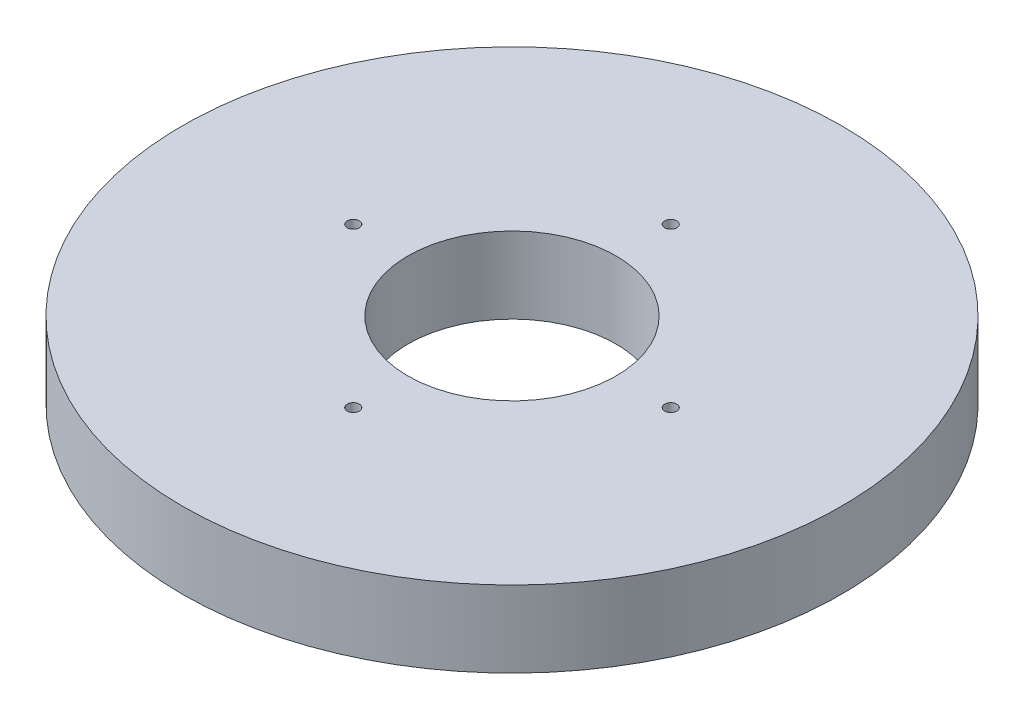
SolidWorks part; units mm, degrees
ref_plane "Front Plane" through (0, 0, 0) normal (0, 0, 1) x (1, 0, 0)
ref_plane "Top Plane" through (0, 0, 0) normal (0, 1, 0) x (1, 0, 0)
ref_plane "Right Plane" through (0, 0, 0) normal (1, 0, 0) x (0, 0, -1)
sketch "Sketch1" plane through (0, 0, 0) normal (0, 1, 0) x (1, 0, 0)
  circle A0 centre (0, 0) radius 95
  dimension "FLANGE_OD" = 190
extrude "Boss-Extrude1" add sketch "Sketch1" along normal blind 22
sketch "Sketch2" plane through (0, 0, 0) normal (0, 1, 0) x (1, 0, 0)
  circle A0 centre (0, 0) radius 30
  dimension "BORE_D" = 60
extrude "Cut-Extrude1" cut sketch "Sketch2" along normal through all
sketch "Sketch3" plane through (0, 22, 0) normal (0, 1, 0) x (1, 0, 0)
  circle A0 centre (0, 0) radius 45.7553 construction
  circle A1 centre (-45.7553, 0) radius 1.7443
  dimension "BOLT_D" = 3.4887
  dimension "BOLT_PCD" = 91.5107
extrude "Cut-Extrude2" cut sketch "Sketch3" against normal blind 21.7511
pattern_circular "CirPattern1" count 4 over 360 about axis through (0, 0, 0) along (0, 1, 0) of "Cut-Extrude2"
